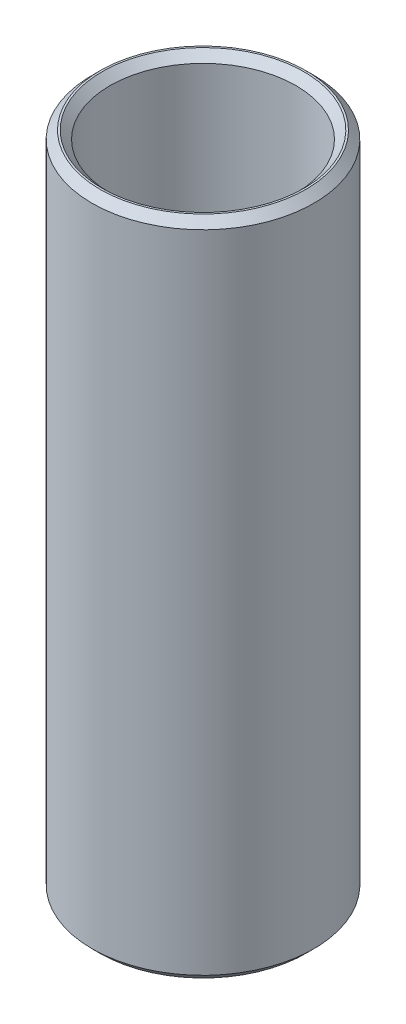
SolidWorks part; units mm, degrees
ref_plane "Front Plane" through (0, 0, 0) normal (0, 0, 1) x (1, 0, 0)
ref_plane "Top Plane" through (0, 0, 0) normal (0, 1, 0) x (1, 0, 0)
ref_plane "Right Plane" through (0, 0, 0) normal (1, 0, 0) x (0, 0, -1)
sketch "Sketch1" plane through (0, 0, 0) normal (0, 1, 0) x (1, 0, 0)
  circle A0 centre (0, 0) radius 35
  dimension "SLEEVE_OD" = 70
extrude "Boss-Extrude1" add sketch "Sketch1" along normal blind 208.7963
sketch "Sketch2" plane through (0, 0, 0) normal (0, 1, 0) x (1, 0, 0)
  circle A0 centre (0, 0) radius 29.346
  dimension "BORE_D" = 58.692
extrude "Cut-Extrude1" cut sketch "Sketch2" along normal through all
chamfer "Chamfer1" distance 2.5274 angle 45 4 edges at (0, 208.7963, 29.346) (0, 0, 29.346) (0, 0, 35) (0, 208.7963, 35)
